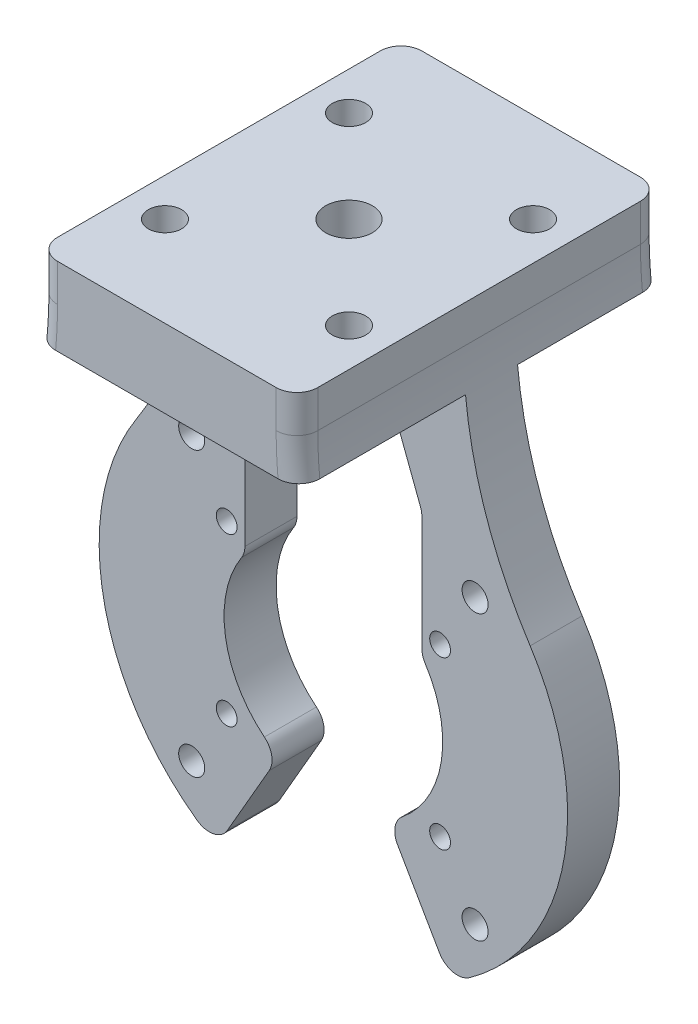
SolidWorks part; units mm, degrees
material "ABS"
ref_plane "前视基准面" through (0, 0, 0) normal (0, 0, 1) x (1, 0, 0)
ref_plane "上视基准面" through (0, 0, 0) normal (0, 1, 0) x (1, 0, 0)
ref_plane "右视基准面" through (0, 0, 0) normal (1, 0, 0) x (0, 0, -1)
sketch "草图1" plane through (0, 0, 0) normal (0, 0, 1) x (1, 0, 0)
  line L0 (55, 0) -> (-55, 0) construction
  line L1 (0, -55) -> (0, 55) construction
  line L2 (-12.5, 18.7083) -> (-12.5, 37.5)
  line L3 (12.5, 18.7083) -> (12.5, 37.5)
  line L4 (0, 0) -> (-11.2314, -19.4963)
  line L5 (0, 0) -> (11.2314, -19.4963)
  line L6 (-12.5, 37.5) -> (12.5, 37.5)
  circle A0 centre (-13.6118, 13.6118) radius 1.25
  circle A6 centre (0, 0) radius 10.5
  circle A7 centre (0, 0) radius 22.5
  circle A8 centre (0, 0) radius 19.25 construction
  circle A9 centre (13.6118, 13.6118) radius 1.25
  circle A10 centre (13.6118, -13.6118) radius 1.25
  circle A11 centre (-13.6118, -13.6118) radius 1.25
  circle A12 centre (-10.25, 8) radius 1
  circle A13 centre (10.25, 8) radius 1
  circle A14 centre (10.25, -8) radius 1
  circle A15 centre (-10.25, -8) radius 1
  point P32 (0, 0)
  dimension "D2" = 38.5
  dimension "D3" = 4
  dimension "D4" = 2.5
  dimension "D5" = 5
  dimension "D7" = 21
  dimension "D8" = 16
  dimension "D9" = 45
  dimension "D12" = 2
  dimension "D6" = 20.5
  dimension "D10" = 25
  dimension "D11" = 37.5
extrude "凸台-拉伸1" add sketch "草图1" along normal blind 5 contours A7 L4 A6 L5 A0 | A7 L3 L6 L2 region at (0, 29.3527, 0) region at (0, 21.8845, 0)
sketch "草图3" plane through (0, 0, 0) normal (1, 0, 0) x (0, 0, -1)
  line L0 (-21, 37.5) -> (14, 37.5)
  line L1 (14, 37.5) -> (14, 30)
  line L2 (14, 30) -> (-21, 30)
  line L6 (-5, 18.7083) -> (-5, 37.5) construction
  line L7 (-5, 37.5) -> (0, 37.5) construction
  line L8 (-21, 37.5) -> (-21, 30)
  dimension "D1" = 7.5
  dimension "D4" = 35
  dimension "D5" = 16
extrude "凸台-拉伸2" add sketch "草图3" along normal mid plane 25
sketch "草图5" plane through (0, 30, 0) normal (0, -1, 0) x (1, 0, 0)
  circle A0 centre (0, 3.5) radius 12.5 construction
  circle A1 centre (-8.8388, 12.3388) radius 1.5
  circle A2 centre (8.8388, 12.3388) radius 1.5
  circle A3 centre (8.8388, -5.3388) radius 1.5
  circle A4 centre (-8.8388, -5.3388) radius 1.5
  circle A5 centre (0, 3.5) radius 2.25
  point P14 (0, 3.5)
  dimension "D2" = 25
  dimension "D3" = 3
  dimension "D4" = 4
  dimension "D5" = 4.5
  dimension "D1" = 3.5
extrude "切除-拉伸1" cut sketch "草图5" against normal mid plane 15 contours A5
fillet "圆角2" radius 40 2 edges at (-12.5, 18.7083, 2.5) (12.5, 18.7083, 2.5)
sketch "草图8" plane through (0, 30, 0) normal (0, -1, 0) x (-1, 0, 0)
  point P0 (8.8388, -12.3388)
  point P3 (-8.8388, -12.3388)
  point P6 (-8.8388, 5.3388)
  point P9 (8.8388, 5.3388)
hole_wizard "M3 六角圆柱头螺钉的柱形沉头孔1" positions "草图8" profile "草图7" counterbore size "M3" standard "GB" end condition through all
sketch "草图7" plane through (-8.8388, 30, 12.3388) normal (1, 0, 0) x (0, 0, -1)
  line L0 (0, 0) -> (0, 7.5)
  line L1 (0, 7.5) -> (1.6, 7.5)
  line L3 (1.6, 7.5) -> (1.6, 3.4)
  line L4 (1.6, 3.4) -> (3, 3.4)
  line L5 (3, 3.4) -> (3, 0)
  line L7 (3, 0) -> (0, 0)
  line L11 (0, -6.35) -> (0, 107.95) construction
  dimension "通孔孔直径" = 3.2
  dimension "通孔孔深度" = 7.5
  dimension "柱形沉头孔直径" = 6
  dimension "柱形沉头孔深度" = 3.4
sketch "草图9" plane through (0, 0, 5) normal (0, 0, 1) x (1, 0, 0)
  line L0 (-12.5, 37.5) -> (12.5, 37.5) construction
  line L1 (-4, 30) -> (-8.5, 18.1644)
  line L2 (-8.5, 6.1644) -> (8.5, 6.1644)
  line L3 (-8.5, 6.1644) -> (-8.5, 18.1644)
  line L5 (8.5, 6.1644) -> (8.5, 18.1644)
  line L8 (-4, 30) -> (4, 30)
  line L10 (4, 30) -> (8.5, 18.1644)
  arc A1 (5.2413, -9.0983) -> (-5.2413, -9.0983) centre (0, 0) ccw construction
  point P12 (0, 30)
  dimension "D1" = 7.5
  dimension "D2" = 17
  dimension "D3" = 8
  dimension "D4" = 12
extrude "切除-拉伸2" cut sketch "草图9" against normal through all
fillet "圆角1" radius 2 18 edges at (11.2314, -19.4963, 2.5) (5.2413, -9.0983, 2.5) (-5.2413, -9.0983, 2.5) (-11.2314, -19.4963, 2.5) (-12.5, 35.7058, -14) (12.5, 35.7058, -14) (-12.548, 31.9535, -14) (12.548, 31.9535, -14) (-8.5, 6.1644, 2.5) (8.5, 6.1644, 2.5) (8.5, 18.1644, 2.5) (4, 30, 2.5) (-8.5, 18.1644, 2.5) (-4, 30, 2.5) (12.548, 31.9535, 21) (-12.548, 31.9535, 21) (12.5, 35.7058, 21) (-12.5, 35.7058, 21)
